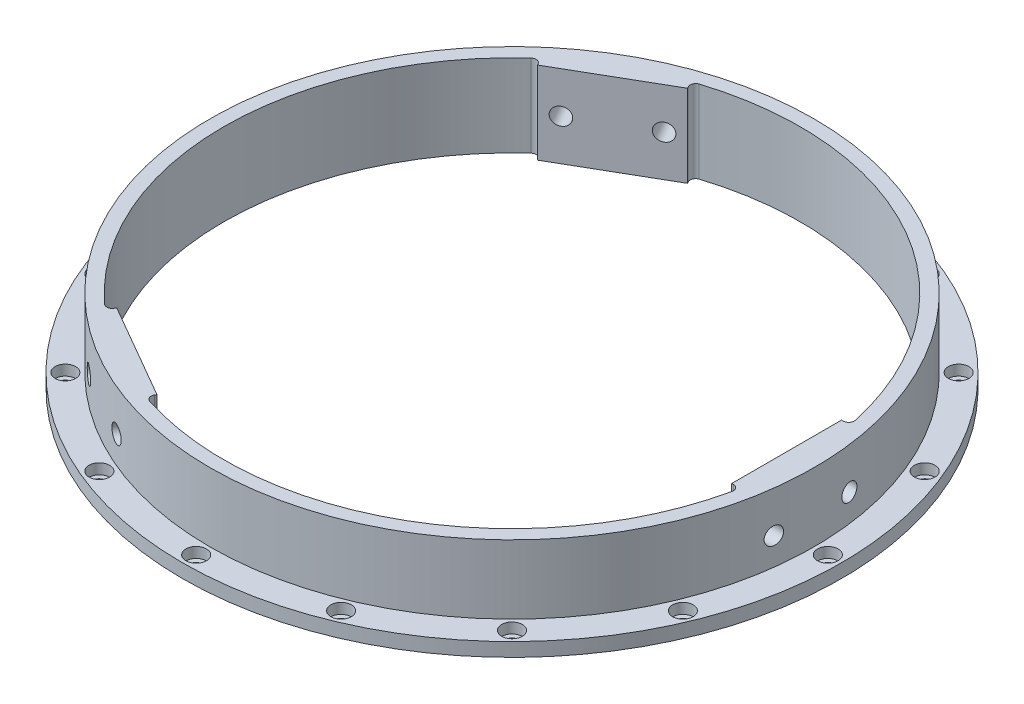
SolidWorks part; units mm, degrees
ref_plane "Front Plane" through (0, 0, 0) normal (0, 0, 1) x (1, 0, 0)
ref_plane "Top Plane" through (0, 0, 0) normal (0, 1, 0) x (1, 0, 0)
ref_plane "Right Plane" through (0, 0, 0) normal (1, 0, 0) x (0, 0, -1)
sketch "Sketch1" plane through (0, 0, 0) normal (0, 1, 0) x (1, 0, 0)
  circle A0 centre (0, 0) radius 152.4
  circle A1 centre (0, 0) radius 133.35
  dimension "D1" = 304.8
  dimension "D2" = 266.7
extrude "Boss-Extrude1" add sketch "Sketch1" along normal blind 38.1
sketch "Sketch2" plane through (0, 38.1, 0) normal (0, 1, 0) x (1, 0, 0)
  circle A0 centre (0, 0) radius 139.7
  circle A1 centre (0, 0) radius 152.4 construction
  circle A2 centre (0, 0) radius 152.4
  dimension "D1" = 279.4
extrude "Cut-Extrude1" cut sketch "Sketch2" against normal blind 31.75
sketch "Sketch3" plane through (0, 38.1, 0) normal (0, 1, 0) x (1, 0, 0)
  line L0 (127, 25.4) -> (127, -25.4)
  line L1 (127, 25.4) -> (130.9086, 25.4)
  line L2 (127, -25.4) -> (130.9086, -25.4)
  circle A0 centre (0, 0) radius 133.35 construction
  arc A1 (130.9086, -25.4) -> (130.9086, 25.4) centre (0, 0) ccw
  point P2 (127, 0)
  dimension "D1" = 50.8
  dimension "D2" = 127
extrude "Boss-Extrude2" add sketch "Sketch3" against normal through all
fillet "Fillet1" radius 2.54 2 edges at (130.9086, 19.05, -25.4) (130.9086, 19.05, 25.4)
hole_wizard "Hole1" positions "Sketch4" profile "Sketch5" legacy end condition through all
sketch "Sketch4" plane through (127, 0, -417.9439) normal (-1, 0, 0) x (0, 0, 1)
  line L6 (392.5439, 0) -> (443.3439, 0) construction
  line L7 (417.9439, 19.05) -> (417.9439, 0)
  line L8 (400.4814, 19.05) -> (435.4064, 19.05)
  line L10 (435.4064, 19.05) -> (443.3439, 19.05)
  line L11 (443.3439, 0) -> (443.3439, 38.1) construction
  point P0 (400.4814, 19.05)
  point P2 (435.4064, 19.05)
  dimension "D1" = 34.925
sketch "Sketch5" plane through (127, 19.05, -17.4625) normal (0, 1, 0) x (0, 0, 1)
  line L0 (0, 0) -> (0, 81.1823)
  line L1 (0, 81.1823) -> (4, 81.1823)
  line L2 (4, 81.1823) -> (4, 0)
  line L3 (4, 0) -> (0, 0)
  line L4 (0, 110) -> (0, -10) construction
  dimension "Diameter" = 8
  dimension "Depth" = 81.1823
pattern_circular "CirPattern1" count 3 over 360 about axis through (0, 38.1, 0) along (0, 1, 0) of "Boss-Extrude2", "Fillet1", "Hole1"
hole_wizard "CBORE for #10 Socket Head Cap Screw1" positions "Sketch6" profile "Sketch8" counterbore size "#10" standard "ANSI Inch"
sketch "Sketch6" plane through (0, 6.35, 0) normal (0, 1, 0) x (1, 0, 0)
  line L0 (0, 0) -> (146.05, 0)
  point P0 (146.05, 0)
  dimension "D1" = 146.05
sketch "Sketch8" plane through (146.05, 6.35, 0) normal (1, 0, 0) x (0, 0, 1)
  line L0 (0, 0) -> (0, 9.4078)
  line L1 (0, 9.4078) -> (2.5527, 7.874)
  line L2 (2.5527, 7.874) -> (2.5527, 4.826)
  line L3 (2.5527, 4.826) -> (4.7625, 4.826)
  line L4 (4.7625, 4.826) -> (4.7625, 0)
  line L5 (4.7625, 0) -> (0, 0)
  line L10 (0, 9.4078) -> (-2.5527, 7.874) construction
  line L11 (0, -6.35) -> (0, 107.95) construction
  dimension "Hole Dia." = 5.1054
  dimension "Hole Depth" = 7.874
  dimension "C'Bore Dia." = 9.525
  dimension "C'Bore Depth" = 4.826
  dimension "Drill Angle" = 118
pattern_circular "CirPattern2" count 16 over 360 about axis through (0, 6.35, 0) along (0, 1, 0) of "CBORE for #10 Socket Head Cap Screw1"
